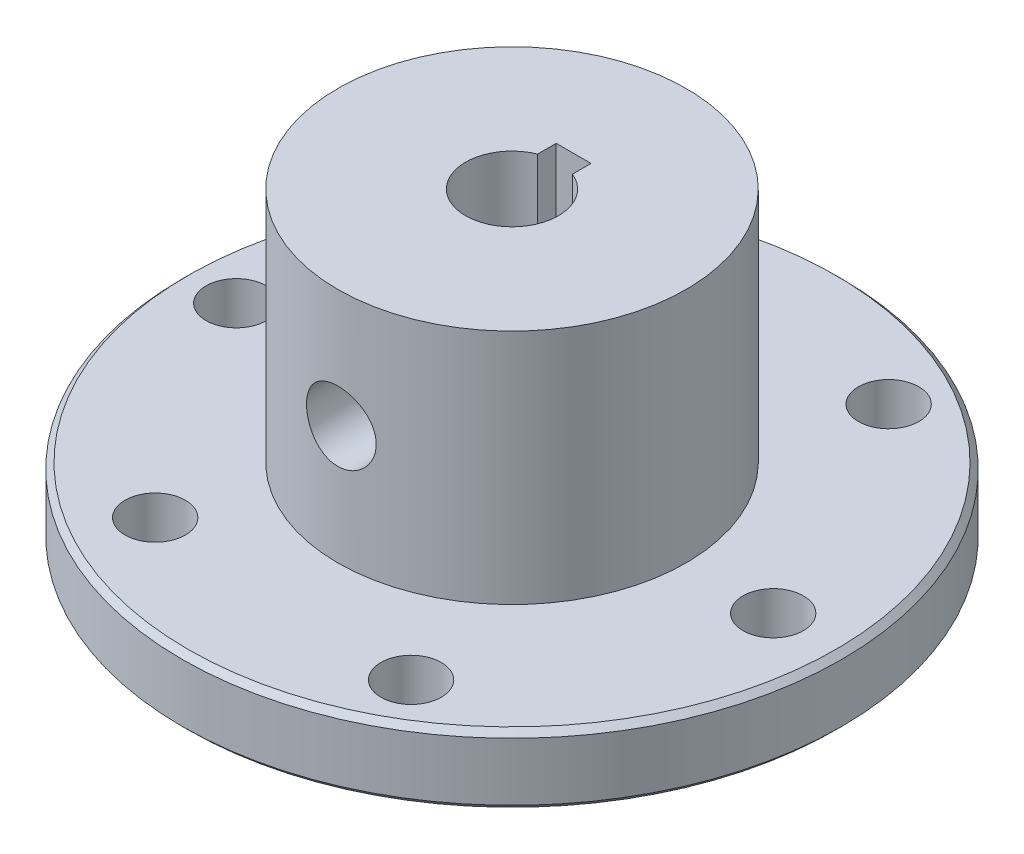
SolidWorks part; units mm, degrees
ref_plane "前视基准面" through (0, 0, 0) normal (0, 0, 1) x (1, 0, 0)
ref_plane "上视基准面" through (0, 0, 0) normal (0, 1, 0) x (1, 0, 0)
ref_plane "右视基准面" through (0, 0, 0) normal (1, 0, 0) x (0, 0, -1)
other "Configuration Table"
sketch "草图1" plane through (0, 0, 0) normal (0, 1, 0) x (1, 0, 0)
  circle A0 centre (0, 0) radius 28.4
  dimension "D1" = 56.8
extrude "凸台-拉伸1" add sketch "草图1" along normal blind 6
sketch "草图2" plane through (0, 0, 0) normal (0, 1, 0) x (1, 0, 0)
  circle A0 centre (0, 0) radius 15
  dimension "D1" = 30
extrude "凸台-拉伸2" add sketch "草图2" along normal blind 20.4 from surface starting at face at (0, 6, 28.4)
sketch "草图3" plane through (0, 0, 0) normal (0, 1, 0) x (1, 0, 0)
  circle A0 centre (0, 0) radius 4
  dimension "D1" = 8
extrude "切除-拉伸1" cut sketch "草图3" along normal up to surface (26.4 mm away) from surface up to face at (0, 26.4, 15) starting at face at (0, 0, 28.4)
sketch "草图4" plane through (0, 0, 0) normal (0, 1, 0) x (1, 0, 0)
  line L0 (-1000, 0) -> (49000, 0) construction
  line L1 (0, -1000) -> (0, 49000) construction
  line L2 (0, 0) -> (25000, 43301.2702) construction
  line L3 (0, 0) -> (-25000, 43301.2702) construction
  circle A0 centre (0, 0) radius 23.75 construction
  circle A7 centre (0, 0) radius 22.5 construction
  circle A8 centre (11.875, 20.5681) radius 2.6
  circle A9 centre (22.5, 0) radius 2.6
  circle A10 centre (11.875, -20.5681) radius 2.6
  circle A11 centre (-11.25, -19.4856) radius 2.6
  circle A12 centre (-23.75, 0) radius 2.6
  circle A13 centre (-11.25, 19.4856) radius 2.6
  dimension "D3" = 47.5
  dimension "D4" = 45
  dimension "D5" = 5.2
  dimension "D6" = 5.2
  dimension "D7" = 5.2
  dimension "D8" = 5.2
  dimension "D9" = 5.2
  dimension "D10" = 5.2
  dimension "D1" = 30
  dimension "D2" = 30
extrude "切除-拉伸3" cut sketch "草图4" against normal up to surface from surface up to face at (0, 0, 4) starting at face at (0, 6, 15)
sketch "草图5" plane through (0, 0, 0) normal (0, 1, 0) x (1, 0, 0)
  line L0 (0, -1000) -> (0, 49000) construction
  line L1 (-1.5, 3.7081) -> (1.5, 3.7081)
  line L2 (1.5, 3.7081) -> (1.5, 5.3081)
  line L3 (1.5, 5.3081) -> (-1.5, 5.3081)
  line L4 (-1.5, 5.3081) -> (-1.5, 3.7081)
  circle A0 centre (0, 0) radius 4 construction
  circle A1 centre (0, 0) radius 4 construction
  point P8 (0, 3.7081)
  dimension "D1" = 3
  dimension "D2" = 1.6
extrude "切除-拉伸4" cut sketch "草图5" against normal up to surface from surface up to face at (-11.25, 0, -16.8856) starting at face at (0, 26.4, 4)
sketch "草图8" plane through (0, 0, 0) normal (0, 1, 0) x (1, 0, 0)
  line L0 (0, -1000) -> (0, 49000) construction
  line L1 (-3, -14.6969) -> (3, -14.6969)
  arc A0 (-3, -14.6969) -> (3, -14.6969) centre (0, 0) ccw
  point P8 (0, -14.6969)
  dimension "D1" = 30
  dimension "D2" = 6
extrude "切除-拉伸5" cut sketch "草图8" against normal up to surface (-6 mm away) from surface up to face at (-11.25, 6, -16.8856) starting at face at (0, 26.4, 15)
sketch "草图6" plane through (0, 0, 0) normal (0, 0, 1) x (1, 0, 0)
  line L0 (15, 26.4) -> (-15, 6) construction
  line L1 (-15, 26.4) -> (15, 26.4) construction
  line L2 (-15, 26.4) -> (-15, 6) construction
  line L3 (-15, 6) -> (15, 6) construction
  line L4 (15, 26.4) -> (15, 6) construction
  line L5 (-15, 26.4) -> (15, 6) construction
  line L7 (-3, 6) -> (3, 6)
  line L8 (-3, 6) -> (-3, 26.4)
  line L9 (-3, 26.4) -> (3, 26.4)
  line L10 (3, 6) -> (3, 26.4)
  line L11 (-3, 6) -> (3, 26.4) construction
  line L12 (-3, 26.4) -> (3, 6) construction
  circle A0 centre (0, 16.2) radius 3
  point P6 (0, 16.2)
  point P7 (0, 16.2)
  dimension "D1" = 6
extrude "凸台-拉伸4" add sketch "草图6" along normal up to surface from surface contours A0 L10 L9 L8 | A0 L8 L7 L10 region at (0, 9.9505, 0) region at (0, 22.4495, 0) up to face at (0, 16.2, -0.1515) starting at face at (0, 16.2, 14.6969)
sketch "草图9" plane through (0, 0, 0) normal (0, 0, 1) x (1, 0, 0)
  circle A0 centre (0, 16.2) radius 3
  point P0 (0, 16.2)
  dimension "D1" = 6
chamfer "倒角1" distance 0.5 angle 45 2 edges at (0, 6, 28.4) (0, 0, 28.4)
extrude "切除-拉伸6" cut sketch "草图9" along normal through all
